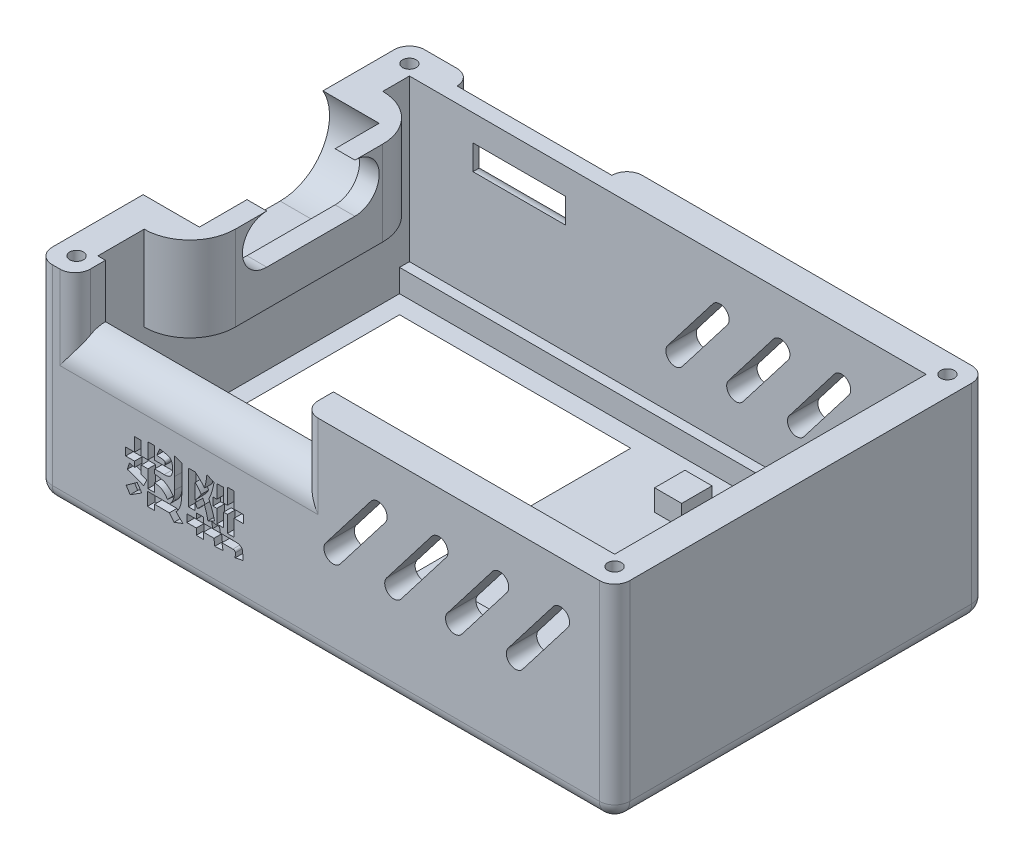
SolidWorks part; units mm, degrees
material "尼龙 6/10"
ref_plane "前视基准面" through (0, 0, 0) normal (0, 0, 1) x (1, 0, 0)
ref_plane "上视基准面" through (0, 0, 0) normal (0, 1, 0) x (1, 0, 0)
ref_plane "右视基准面" through (0, 0, 0) normal (1, 0, 0) x (0, 0, -1)
sketch "草图1" plane through (0, 0, 0) normal (0, 1, 0) x (1, 0, 0)
  line L1 (-72.1576, -30.7504) -> (-34.1576, -30.7504)
  line L2 (-72.1576, -30.7504) -> (-72.1576, -6.2504)
  line L3 (-72.1576, -6.2504) -> (-34.1576, -6.2504)
  line L4 (-34.1576, -30.7504) -> (-34.1576, -6.2504)
  dimension "D1" = 24.5
  dimension "D2" = 38
extrude "凸台-拉伸1" add sketch "草图1" along normal blind 13.58 contours L2 L1 L4 L3
sketch "草图2" plane through (0, 13.58, 0) normal (0, 1, 0) x (1, 0, 0)
  line L0 (-34.1576, -30.7504) -> (-34.1576, -6.2504) construction
  line L1 (-70.1576, -8.2504) -> (-36.1576, -8.2504)
  line L2 (-70.1576, -8.2504) -> (-70.1576, -28.7504)
  line L3 (-70.1576, -28.7504) -> (-36.1576, -28.7504)
  line L4 (-36.1576, -8.2504) -> (-36.1576, -28.7504)
  line L5 (-72.1576, -30.7504) -> (-34.1576, -30.7504) construction
  line L6 (-72.1576, -30.7504) -> (-72.1576, -6.2504) construction
  line L7 (-72.1576, -6.2504) -> (-34.1576, -6.2504) construction
  dimension "D1" = 2
  dimension "D2" = 2
  dimension "D3" = 2
  dimension "D4" = 2
extrude "切除-拉伸1" cut sketch "草图2" against normal blind 10.58
sketch "草图4" plane through (0, 0, 0) normal (0, -1, 0) x (-1, 0, 0)
  line L0 (72.1576, -30.7504) -> (72.1576, -6.2504) construction
  line L1 (68.9576, -10.1004) -> (53.7476, -10.1004)
  line L2 (68.9576, -10.1004) -> (68.9576, -25.3104)
  line L3 (68.9576, -25.3104) -> (53.7476, -25.3104)
  line L4 (53.7476, -10.1004) -> (53.7476, -25.3104)
  line L6 (72.1576, -30.7504) -> (34.1576, -30.7504) construction
  dimension "D1" = 15.21
  dimension "D2" = 15.21
  dimension "D3" = 3.2
  dimension "D4" = 5.44
extrude "切除-拉伸2" cut sketch "草图4" against normal blind 15 contours L2 L1 L4 L3
sketch "草图6" plane through (0, 0, 30.7504) normal (0, 0, 1) x (1, 0, 0)
  line L1 (-54.6576, 10.08) -> (-69.6576, 10.08)
  line L2 (-54.6576, 10.08) -> (-54.6576, 13.58)
  line L3 (-54.6576, 13.58) -> (-69.6576, 13.58)
  line L4 (-69.6576, 10.08) -> (-69.6576, 13.58)
  line L5 (-72.1576, 13.58) -> (-72.1576, 0) construction
  line L6 (-72.1576, 13.58) -> (-34.1576, 13.58) construction
  point P9 (-69.6576, 11.83)
  dimension "D2" = 3.5
  dimension "D3" = 2.5
  dimension "D4" = 15
extrude "切除-拉伸4" cut sketch "草图6" against normal blind 5
sketch "草图11" plane through (0, 3, 0) normal (0, 1, 0) x (1, 0, 0)
  line L0 (-68.9576, -25.3104) -> (-68.9576, -10.1004) construction
  line L1 (-37.6576, -8.9004) -> (-70.1576, -8.9004)
  line L2 (-37.6576, -8.9004) -> (-37.6576, -26.5004)
  line L3 (-37.6576, -26.5004) -> (-70.1576, -26.5004)
  line L4 (-70.1576, -8.9004) -> (-70.1576, -26.5004)
  line L5 (-53.7476, -10.1004) -> (-68.9576, -10.1004) construction
  line L7 (-36.1576, -28.7504) -> (-36.1576, -8.2504) construction
  dimension "D1" = 1.5
  dimension "D2" = 17.6
  dimension "D3" = 1.2
  dimension "D4" = 1.2
extrude "切除-拉伸10" cut sketch "草图11" against normal blind 1.5
fillet "圆角2" radius 1 8 edges at (-34.1576, 6.79, 6.2504) (-53.1576, 0, 6.2504) (-53.1576, 0, 30.7504) (-72.1576, 0, 18.5004) (-72.1576, 6.79, 30.7504) (-34.1576, 6.79, 30.7504) (-34.1576, 0, 18.5004) (-72.1576, 6.79, 6.2504)
chamfer "倒角2" distance 1.5 distance2 1.5 4 edges at (-61.3526, 0, 25.3104) (-53.7476, 0, 17.7054) (-61.3526, 0, 10.1004) (-68.9576, 0, 17.7054)
fillet "圆角8" radius 1 1 edges at (-37.6576, 3, 17.7004) type face fillet first side face at (-37.6576, 2.25, 17.7004) second side face at (-53.5326, 3, 18.1004)
sketch "草图24" plane through (-36.1576, 0, 0) normal (-1, 0, 0) x (0, 0, 1)
  line L1 (21.2004, 3) -> (14.2004, 3)
  line L2 (21.2004, 3) -> (21.2004, 12.5)
  line L3 (21.2004, 12.5) -> (14.2004, 12.5)
  line L4 (14.2004, 3) -> (14.2004, 12.5)
  line L10 (8.9004, 3) -> (26.5004, 3) construction
  point P4 (17.7004, 3)
  dimension "D1" = 9.5
  dimension "D2" = 7
extrude "切除-拉伸17" cut sketch "草图24" against normal blind 1
sketch "草图29" plane through (0, 13.58, 0) normal (0, 1, 0) x (1, 0, 0)
  line L0 (-72.1576, -29.7504) -> (-72.1576, -7.2504) construction
  line L4 (-34.1576, -29.7504) -> (-34.1576, -7.2504) construction
  line L5 (-71.1576, -30.7504) -> (-69.6576, -30.7504) construction
  line L8 (-71.1576, -6.2504) -> (-35.1576, -6.2504) construction
  circle A0 centre (-70.8576, -7.5504) radius 0.45
  circle A1 centre (-70.8576, -29.4504) radius 0.45
  circle A2 centre (-35.4576, -7.5504) radius 0.45
  circle A3 centre (-35.4576, -29.4504) radius 0.45
  dimension "D1" = 0.9
  dimension "D2" = 1.3
  dimension "D3" = 1.3
  dimension "D4" = 1.3
  dimension "D5" = 1.3
extrude "切除-拉伸18" cut sketch "草图29" against normal blind 6
sketch "草图37" plane through (0, 13.58, 0) normal (0, 1, 0) x (1, 0, 0)
  line L0 (-70.1576, -8.2504) -> (-70.1576, -28.7504) construction
  line L1 (-70.1576, -10.0054) -> (-67.1576, -10.0054)
  line L2 (-70.1576, -10.0054) -> (-70.1576, -25.7054)
  line L3 (-70.1576, -25.7054) -> (-67.1576, -25.7054)
  line L4 (-67.1576, -10.0054) -> (-67.1576, -25.7054)
  dimension "D1" = 3
  dimension "D2" = 15.7
extrude "凸台-拉伸8" add sketch "草图37" against normal blind 10
sketch "草图34" plane through (-72.1576, 0, 0) normal (-1, 0, 0) x (0, 0, 1)
  line L0 (20.9554, 11.955) -> (14.7554, 11.955) construction
  line L3 (20.9554, 8.705) -> (14.7554, 8.705)
  line L4 (20.9554, 15.205) -> (14.7554, 15.205)
  line L5 (10.0054, 3.58) -> (10.0054, 13.58) construction
  line L6 (29.7504, 13.58) -> (7.2504, 13.58) construction
  line L12 (7.2504, 1) -> (29.7504, 1) construction
  arc A2 (20.9554, 8.705) -> (20.9554, 15.205) centre (20.9554, 11.955) ccw
  arc A3 (14.7554, 15.205) -> (14.7554, 8.705) centre (14.7554, 11.955) ccw
  point P3 (17.8554, 11.955)
  point P8 (17.8554, 15.205)
  point P15 (18.5004, 1)
  dimension "D3" = 1.625
  dimension "D4" = 4.75
  dimension "D1" = 6.2
  dimension "D2" = 6.5
extrude "切除-拉伸21" cut sketch "草图34" against normal blind 3.7
sketch "草图39" plane through (-68.4576, 0, 0) normal (-1, 0, 0) x (0, 0, 1)
  line L0 (20.6371, 11.98) -> (14.8371, 11.98) construction
  line L1 (20.6371, 10.38) -> (14.8371, 10.38)
  line L2 (20.6371, 13.58) -> (14.8371, 13.58)
  line L3 (11.9408, 13.58) -> (23.77, 13.58) construction
  arc A0 (20.6371, 10.38) -> (20.6371, 13.58) centre (20.6371, 11.98) ccw
  arc A1 (14.8371, 13.58) -> (14.8371, 10.38) centre (14.8371, 11.98) ccw
  point P2 (17.7371, 11.98)
  point P7 (22.2371, 11.98)
  point P8 (13.2371, 11.98)
  dimension "D1" = 3.2
  dimension "D2" = 9
extrude "切除-拉伸24" cut sketch "草图39" against normal blind 9 contours L1 A1 L2 A0
fillet "圆角9" radius 3 2 edges at (-67.1576, 8.58, 10.0054) (-67.1576, 8.58, 25.7054)
sketch "草图42" plane through (0, 0, 6.2504) normal (0, 0, -1) x (-1, 0, 0)
  line L0 (72.1576, 13.58) -> (72.1576, 1) construction
  text T0 "<b><r270>关开</r></b>" font "微软雅黑" height 3
  point P1 (60.1576, 5.864)
  point P2 (60.1576, 6.3989)
  dimension "D1" = 12
extrude "切除-拉伸26" cut sketch "草图42" against normal blind 0.5
sketch "草图43" plane through (0, 0, 30.7504) normal (0, 0, 1) x (1, 0, 0)
  text T0 "<b><r90>选择</r></b>" font "微软雅黑" height 3
  point P0 (-63.0353, 2.8105)
extrude "切除-拉伸27" cut sketch "草图43" against normal blind 0.5
sketch "草图46" plane through (-67.1576, 0, 0) normal (1, 0, 0) x (0, 0, -1)
  line L7 (-8.2504, 3) -> (-8.2504, 13.58) construction
  line L8 (-28.7504, 3) -> (-28.7504, 13.58) construction
  line L19 (-28.7504, 8) -> (-8.2504, 8)
  line L20 (-28.7504, 8) -> (-28.7504, 3)
  line L21 (-28.7504, 3) -> (-8.2504, 3)
  line L22 (-8.2504, 8) -> (-8.2504, 3)
  line L25 (-8.2504, 3) -> (-8.9004, 3) construction
  dimension "D1" = 5
extrude "切除-拉伸29" cut sketch "草图46" against normal up to surface (3 mm away) and the other way up to surface (31 mm away) up to face at (-70.1576, 6.3733, 18.0188) other way up to face at (-36.1576, 8.02, 18.1004)
sketch "草图48" plane through (0, 1.5, 0) normal (0, 1, 0) x (1, 0, 0)
  line L0 (-70.1576, -8.2504) -> (-70.1576, -8.9004) construction
  line L1 (-49.3076, -10.9679) -> (-47.5264, -10.9679)
  line L2 (-49.3076, -10.9679) -> (-49.3076, -12.9679)
  line L3 (-49.3076, -12.9679) -> (-47.5264, -12.9679)
  line L4 (-47.5264, -10.9679) -> (-47.5264, -12.9679)
  line L5 (-49.3076, -25.3179) -> (-47.5264, -25.3179)
  line L6 (-49.3076, -25.3179) -> (-49.3076, -27.3179)
  line L7 (-49.3076, -27.3179) -> (-47.5264, -27.3179)
  line L8 (-47.5264, -25.3179) -> (-47.5264, -27.3179)
  dimension "D1" = 20.85
  dimension "D2" = 2
  dimension "D3" = 12.35
extrude "凸台-拉伸9" add sketch "草图48" along normal blind 1.4
sketch "草图49" plane through (0, 3, 0) normal (0, 1, 0) x (1, 0, 0)
  line L1 (-36.6576, -14.2004) -> (-37.6576, -14.2004)
  line L2 (-36.6576, -14.2004) -> (-36.6576, -21.2004)
  line L3 (-36.6576, -21.2004) -> (-37.6576, -21.2004)
  line L4 (-37.6576, -14.2004) -> (-37.6576, -21.2004)
  line L5 (-37.6576, -26.5004) -> (-37.6576, -8.9004) construction
  line L11 (-36.6576, -8.9004) -> (-36.6576, -26.5004) construction
  point P4 (-36.6576, -17.7004)
  dimension "D1" = 7
extrude "切除-拉伸30" cut sketch "草图49" against normal up to surface (1.5 mm away) up to face at (-48.417, 1.5, 11.9679)
sketch "草图50" plane through (0, 0, 6.2504) normal (0, 0, -1) x (-1, 0, 0)
  line L0 (49.7213, 10.2108) -> (52.6822, 6.3661) construction
  line L1 (50.1967, 10.5769) -> (53.1576, 6.7322)
  line L2 (49.2459, 9.8448) -> (52.2068, 6)
  line L3 (45.7213, 10.2108) -> (48.6822, 6.3661) construction
  line L4 (46.1967, 10.5769) -> (49.1576, 6.7322)
  line L5 (45.2459, 9.8448) -> (48.2068, 6)
  line L6 (41.7213, 10.2108) -> (44.6822, 6.3661) construction
  line L7 (42.1967, 10.5769) -> (45.1576, 6.7322)
  line L8 (41.2459, 9.8448) -> (44.2068, 6)
  line L9 (37.7213, 10.2108) -> (40.6822, 6.3661) construction
  line L10 (38.1967, 10.5769) -> (41.1576, 6.7322)
  line L11 (37.2459, 9.8448) -> (40.2068, 6)
  line L12 (71.1576, 1) -> (71.1576, 13.58) construction
  line L13 (35.1576, 1) -> (71.1576, 1) construction
  arc A0 (50.1967, 10.5769) -> (49.2459, 9.8448) centre (49.7213, 10.2108) ccw
  arc A1 (52.2068, 6) -> (53.1576, 6.7322) centre (52.6822, 6.3661) ccw
  arc A2 (46.1967, 10.5769) -> (45.2459, 9.8448) centre (45.7213, 10.2108) ccw
  arc A3 (48.2068, 6) -> (49.1576, 6.7322) centre (48.6822, 6.3661) ccw
  arc A4 (42.1967, 10.5769) -> (41.2459, 9.8448) centre (41.7213, 10.2108) ccw
  arc A5 (44.2068, 6) -> (45.1576, 6.7322) centre (44.6822, 6.3661) ccw
  arc A6 (38.1967, 10.5769) -> (37.2459, 9.8448) centre (37.7213, 10.2108) ccw
  arc A7 (40.2068, 6) -> (41.1576, 6.7322) centre (40.6822, 6.3661) ccw
  point P2 (51.2018, 8.2885)
  point P11 (47.2018, 8.2885)
  point P18 (43.2018, 8.2885)
  point P25 (39.2018, 8.2885)
  dimension "D4" = 4.8527
  dimension "D2" = 18
  dimension "D3" = 5
  dimension "D1" = 4
extrude "切除-拉伸31" cut sketch "草图50" against normal through all
sketch "草图51" plane through (0, 0, 0) normal (0, -1, 0) x (1, 0, 0)
  line L0 (-50.2476, 26.8104) -> (-48.2476, 26.8104)
  line L1 (-39.1576, 26.8104) -> (-37.1576, 26.8104)
  line L2 (-39.1576, 26.8104) -> (-39.1576, 9.2504)
  line L3 (-39.1576, 9.2504) -> (-37.1576, 9.2504)
  line L4 (-37.1576, 26.8104) -> (-37.1576, 9.2504)
  line L5 (-50.2476, 26.8104) -> (-50.2476, 9.2504)
  line L6 (-50.2476, 9.2504) -> (-48.2476, 9.2504)
  line L7 (-48.2476, 26.8104) -> (-48.2476, 9.2504)
  line L8 (-52.2476, 26.8104) -> (-52.2476, 8.6004) construction
  line L9 (-35.1576, 7.2504) -> (-35.1576, 29.7504) construction
  line L10 (-71.1576, 7.2504) -> (-35.1576, 7.2504) construction
  line L11 (-70.4576, 26.8104) -> (-52.2476, 26.8104) construction
  dimension "D1" = 2
  dimension "D2" = 2
  dimension "D4" = 2
  dimension "D5" = 2
extrude "切除-拉伸32" cut sketch "草图51" against normal blind 0.5
sketch "草图52" plane through (0, 0.5, 0) normal (0, -1, 0) x (1, 0, 0)
  line L0 (-50.2476, 26.8104) -> (-50.2476, 9.2504) construction
  line L1 (-50.2476, 26.5104) -> (-48.2476, 26.5104)
  line L2 (-50.2476, 26.5104) -> (-50.2476, 26.0104)
  line L3 (-50.2476, 26.0104) -> (-48.2476, 26.0104)
  line L4 (-48.2476, 26.5104) -> (-48.2476, 26.0104)
  line L5 (-48.2476, 9.2504) -> (-48.2476, 26.8104) construction
  line L6 (-48.2476, 26.8104) -> (-50.2476, 26.8104) construction
  line L7 (-39.1576, 26.5104) -> (-39.1576, 26.0104)
  line L8 (-39.1576, 26.5104) -> (-37.1576, 26.5104)
  line L9 (-37.1576, 26.5104) -> (-37.1576, 26.0104)
  line L10 (-39.1576, 26.0104) -> (-37.1576, 26.0104)
  line L11 (-39.1576, 25.7486) -> (-39.1576, 25.2486)
  line L12 (-39.1576, 25.7486) -> (-37.1576, 25.7486)
  line L13 (-37.1576, 25.7486) -> (-37.1576, 25.2486)
  line L14 (-39.1576, 25.2486) -> (-37.1576, 25.2486)
  line L15 (-39.1576, 24.9868) -> (-39.1576, 24.4868)
  line L16 (-39.1576, 24.9868) -> (-37.1576, 24.9868)
  line L17 (-37.1576, 24.9868) -> (-37.1576, 24.4868)
  line L18 (-39.1576, 24.4868) -> (-37.1576, 24.4868)
  line L19 (-39.1576, 24.225) -> (-39.1576, 23.725)
  line L20 (-39.1576, 24.225) -> (-37.1576, 24.225)
  line L21 (-37.1576, 24.225) -> (-37.1576, 23.725)
  line L22 (-39.1576, 23.725) -> (-37.1576, 23.725)
  line L23 (-39.1576, 23.4631) -> (-39.1576, 22.9631)
  line L24 (-39.1576, 23.4631) -> (-37.1576, 23.4631)
  line L25 (-37.1576, 23.4631) -> (-37.1576, 22.9631)
  line L26 (-39.1576, 22.9631) -> (-37.1576, 22.9631)
  line L27 (-39.1576, 22.7013) -> (-39.1576, 22.2013)
  line L28 (-39.1576, 22.7013) -> (-37.1576, 22.7013)
  line L29 (-37.1576, 22.7013) -> (-37.1576, 22.2013)
  line L30 (-39.1576, 22.2013) -> (-37.1576, 22.2013)
  line L31 (-39.1576, 21.9395) -> (-39.1576, 21.4395)
  line L32 (-39.1576, 21.9395) -> (-37.1576, 21.9395)
  line L33 (-37.1576, 21.9395) -> (-37.1576, 21.4395)
  line L34 (-39.1576, 21.4395) -> (-37.1576, 21.4395)
  line L35 (-39.1576, 21.1777) -> (-39.1576, 20.6777)
  line L36 (-39.1576, 21.1777) -> (-37.1576, 21.1777)
  line L37 (-37.1576, 21.1777) -> (-37.1576, 20.6777)
  line L38 (-39.1576, 20.6777) -> (-37.1576, 20.6777)
  line L39 (-39.1576, 20.4159) -> (-39.1576, 19.9159)
  line L40 (-39.1576, 20.4159) -> (-37.1576, 20.4159)
  line L41 (-37.1576, 20.4159) -> (-37.1576, 19.9159)
  line L42 (-39.1576, 19.9159) -> (-37.1576, 19.9159)
  line L43 (-39.1576, 19.6541) -> (-39.1576, 19.1541)
  line L44 (-39.1576, 19.6541) -> (-37.1576, 19.6541)
  line L45 (-37.1576, 19.6541) -> (-37.1576, 19.1541)
  line L46 (-39.1576, 19.1541) -> (-37.1576, 19.1541)
  line L47 (-39.1576, 18.8922) -> (-39.1576, 18.3922)
  line L48 (-39.1576, 18.8922) -> (-37.1576, 18.8922)
  line L49 (-37.1576, 18.8922) -> (-37.1576, 18.3922)
  line L50 (-39.1576, 18.3922) -> (-37.1576, 18.3922)
  line L51 (-39.1576, 18.1304) -> (-39.1576, 17.6304)
  line L52 (-39.1576, 18.1304) -> (-37.1576, 18.1304)
  line L53 (-37.1576, 18.1304) -> (-37.1576, 17.6304)
  line L54 (-39.1576, 17.6304) -> (-37.1576, 17.6304)
  line L55 (-39.1576, 17.3686) -> (-39.1576, 16.8686)
  line L56 (-39.1576, 17.3686) -> (-37.1576, 17.3686)
  line L57 (-37.1576, 17.3686) -> (-37.1576, 16.8686)
  line L58 (-39.1576, 16.8686) -> (-37.1576, 16.8686)
  line L59 (-39.1576, 16.6068) -> (-39.1576, 16.1068)
  line L60 (-39.1576, 16.6068) -> (-37.1576, 16.6068)
  line L61 (-37.1576, 16.6068) -> (-37.1576, 16.1068)
  line L62 (-39.1576, 16.1068) -> (-37.1576, 16.1068)
  line L63 (-39.1576, 15.845) -> (-39.1576, 15.345)
  line L64 (-39.1576, 15.845) -> (-37.1576, 15.845)
  line L65 (-37.1576, 15.845) -> (-37.1576, 15.345)
  line L66 (-39.1576, 15.345) -> (-37.1576, 15.345)
  line L67 (-39.1576, 15.0831) -> (-39.1576, 14.5831)
  line L68 (-39.1576, 15.0831) -> (-37.1576, 15.0831)
  line L69 (-37.1576, 15.0831) -> (-37.1576, 14.5831)
  line L70 (-39.1576, 14.5831) -> (-37.1576, 14.5831)
  line L71 (-39.1576, 14.3213) -> (-39.1576, 13.8213)
  line L72 (-39.1576, 14.3213) -> (-37.1576, 14.3213)
  line L73 (-37.1576, 14.3213) -> (-37.1576, 13.8213)
  line L74 (-39.1576, 13.8213) -> (-37.1576, 13.8213)
  line L75 (-50.2476, 25.7486) -> (-50.2476, 25.2486)
  line L76 (-50.2476, 25.7486) -> (-48.2476, 25.7486)
  line L77 (-48.2476, 25.7486) -> (-48.2476, 25.2486)
  line L78 (-50.2476, 25.2486) -> (-48.2476, 25.2486)
  line L79 (-50.2476, 24.9868) -> (-50.2476, 24.4868)
  line L80 (-50.2476, 24.9868) -> (-48.2476, 24.9868)
  line L81 (-48.2476, 24.9868) -> (-48.2476, 24.4868)
  line L82 (-50.2476, 24.4868) -> (-48.2476, 24.4868)
  line L83 (-50.2476, 24.225) -> (-50.2476, 23.725)
  line L84 (-50.2476, 24.225) -> (-48.2476, 24.225)
  line L85 (-48.2476, 24.225) -> (-48.2476, 23.725)
  line L86 (-50.2476, 23.725) -> (-48.2476, 23.725)
  line L87 (-50.2476, 23.4631) -> (-50.2476, 22.9631)
  line L88 (-50.2476, 23.4631) -> (-48.2476, 23.4631)
  line L89 (-48.2476, 23.4631) -> (-48.2476, 22.9631)
  line L90 (-50.2476, 22.9631) -> (-48.2476, 22.9631)
  line L91 (-50.2476, 22.7013) -> (-50.2476, 22.2013)
  line L92 (-50.2476, 22.7013) -> (-48.2476, 22.7013)
  line L93 (-48.2476, 22.7013) -> (-48.2476, 22.2013)
  line L94 (-50.2476, 22.2013) -> (-48.2476, 22.2013)
  line L95 (-50.2476, 21.9395) -> (-50.2476, 21.4395)
  line L96 (-50.2476, 21.9395) -> (-48.2476, 21.9395)
  line L97 (-48.2476, 21.9395) -> (-48.2476, 21.4395)
  line L98 (-50.2476, 21.4395) -> (-48.2476, 21.4395)
  line L99 (-50.2476, 21.1777) -> (-50.2476, 20.6777)
  line L100 (-50.2476, 21.1777) -> (-48.2476, 21.1777)
  line L101 (-48.2476, 21.1777) -> (-48.2476, 20.6777)
  line L102 (-50.2476, 20.6777) -> (-48.2476, 20.6777)
  line L103 (-50.2476, 20.4159) -> (-50.2476, 19.9159)
  line L104 (-50.2476, 20.4159) -> (-48.2476, 20.4159)
  line L105 (-48.2476, 20.4159) -> (-48.2476, 19.9159)
  line L106 (-50.2476, 19.9159) -> (-48.2476, 19.9159)
  line L107 (-50.2476, 19.6541) -> (-50.2476, 19.1541)
  line L108 (-50.2476, 19.6541) -> (-48.2476, 19.6541)
  line L109 (-48.2476, 19.6541) -> (-48.2476, 19.1541)
  line L110 (-50.2476, 19.1541) -> (-48.2476, 19.1541)
  line L111 (-50.2476, 18.8922) -> (-50.2476, 18.3922)
  line L112 (-50.2476, 18.8922) -> (-48.2476, 18.8922)
  line L113 (-48.2476, 18.8922) -> (-48.2476, 18.3922)
  line L114 (-50.2476, 18.3922) -> (-48.2476, 18.3922)
  line L115 (-50.2476, 18.1304) -> (-50.2476, 17.6304)
  line L116 (-50.2476, 18.1304) -> (-48.2476, 18.1304)
  line L117 (-48.2476, 18.1304) -> (-48.2476, 17.6304)
  line L118 (-50.2476, 17.6304) -> (-48.2476, 17.6304)
  line L119 (-50.2476, 17.3686) -> (-50.2476, 16.8686)
  line L120 (-50.2476, 17.3686) -> (-48.2476, 17.3686)
  line L121 (-48.2476, 17.3686) -> (-48.2476, 16.8686)
  line L122 (-50.2476, 16.8686) -> (-48.2476, 16.8686)
  line L123 (-50.2476, 16.6068) -> (-50.2476, 16.1068)
  line L124 (-50.2476, 16.6068) -> (-48.2476, 16.6068)
  line L125 (-48.2476, 16.6068) -> (-48.2476, 16.1068)
  line L126 (-50.2476, 16.1068) -> (-48.2476, 16.1068)
  line L127 (-50.2476, 15.845) -> (-50.2476, 15.345)
  line L128 (-50.2476, 15.845) -> (-48.2476, 15.845)
  line L129 (-48.2476, 15.845) -> (-48.2476, 15.345)
  line L130 (-50.2476, 15.345) -> (-48.2476, 15.345)
  line L131 (-50.2476, 15.0831) -> (-50.2476, 14.5831)
  line L132 (-50.2476, 15.0831) -> (-48.2476, 15.0831)
  line L133 (-48.2476, 15.0831) -> (-48.2476, 14.5831)
  line L134 (-50.2476, 14.5831) -> (-48.2476, 14.5831)
  line L135 (-50.2476, 14.3213) -> (-50.2476, 13.8213)
  line L136 (-50.2476, 14.3213) -> (-48.2476, 14.3213)
  line L137 (-48.2476, 14.3213) -> (-48.2476, 13.8213)
  line L138 (-50.2476, 13.8213) -> (-48.2476, 13.8213)
  line L139 (-50.2476, 13.5595) -> (-50.2476, 13.0595)
  line L140 (-50.2476, 13.5595) -> (-48.2476, 13.5595)
  line L141 (-48.2476, 13.5595) -> (-48.2476, 13.0595)
  line L142 (-50.2476, 13.0595) -> (-48.2476, 13.0595)
  line L143 (-39.1576, 13.5595) -> (-39.1576, 13.0595)
  line L144 (-39.1576, 13.5595) -> (-37.1576, 13.5595)
  line L145 (-37.1576, 13.5595) -> (-37.1576, 13.0595)
  line L146 (-39.1576, 13.0595) -> (-37.1576, 13.0595)
  line L147 (-50.2476, 12.7977) -> (-50.2476, 12.2977)
  line L148 (-50.2476, 12.7977) -> (-48.2476, 12.7977)
  line L149 (-48.2476, 12.7977) -> (-48.2476, 12.2977)
  line L150 (-50.2476, 12.2977) -> (-48.2476, 12.2977)
  line L151 (-39.1576, 12.7977) -> (-39.1576, 12.2977)
  line L152 (-39.1576, 12.7977) -> (-37.1576, 12.7977)
  line L153 (-37.1576, 12.7977) -> (-37.1576, 12.2977)
  line L154 (-39.1576, 12.2977) -> (-37.1576, 12.2977)
  line L155 (-50.2476, 12.0359) -> (-50.2476, 11.5359)
  line L156 (-50.2476, 12.0359) -> (-48.2476, 12.0359)
  line L157 (-48.2476, 12.0359) -> (-48.2476, 11.5359)
  line L158 (-50.2476, 11.5359) -> (-48.2476, 11.5359)
  line L159 (-39.1576, 12.0359) -> (-39.1576, 11.5359)
  line L160 (-39.1576, 12.0359) -> (-37.1576, 12.0359)
  line L161 (-37.1576, 12.0359) -> (-37.1576, 11.5359)
  line L162 (-39.1576, 11.5359) -> (-37.1576, 11.5359)
  line L163 (-50.2476, 11.2741) -> (-50.2476, 10.7741)
  line L164 (-50.2476, 11.2741) -> (-48.2476, 11.2741)
  line L165 (-48.2476, 11.2741) -> (-48.2476, 10.7741)
  line L166 (-50.2476, 10.7741) -> (-48.2476, 10.7741)
  line L167 (-39.1576, 11.2741) -> (-39.1576, 10.7741)
  line L168 (-39.1576, 11.2741) -> (-37.1576, 11.2741)
  line L169 (-37.1576, 11.2741) -> (-37.1576, 10.7741)
  line L170 (-39.1576, 10.7741) -> (-37.1576, 10.7741)
  line L171 (-50.2476, 10.5122) -> (-50.2476, 10.0122)
  line L172 (-50.2476, 10.5122) -> (-48.2476, 10.5122)
  line L173 (-48.2476, 10.5122) -> (-48.2476, 10.0122)
  line L174 (-50.2476, 10.0122) -> (-48.2476, 10.0122)
  line L175 (-39.1576, 10.5122) -> (-39.1576, 10.0122)
  line L176 (-39.1576, 10.5122) -> (-37.1576, 10.5122)
  line L177 (-37.1576, 10.5122) -> (-37.1576, 10.0122)
  line L178 (-39.1576, 10.0122) -> (-37.1576, 10.0122)
  line L179 (-50.2476, 9.7504) -> (-50.2476, 9.2504)
  line L180 (-50.2476, 9.7504) -> (-48.2476, 9.7504)
  line L181 (-48.2476, 9.7504) -> (-48.2476, 9.2504)
  line L182 (-50.2476, 9.2504) -> (-48.2476, 9.2504)
  line L183 (-39.1576, 9.7504) -> (-39.1576, 9.2504)
  line L184 (-39.1576, 9.7504) -> (-37.1576, 9.7504)
  line L185 (-37.1576, 9.7504) -> (-37.1576, 9.2504)
  line L186 (-39.1576, 9.2504) -> (-37.1576, 9.2504)
  line L187 (-39.1576, 26.8104) -> (-39.1576, 9.2504) construction
  line L188 (-39.1576, 9.2504) -> (-37.1576, 9.2504) construction
  dimension "D1" = 0.5
  dimension "D2" = 0.3
  dimension "D3" = 2
  dimension "D4" = 23
extrude "凸台-拉伸10" add sketch "草图52" along normal blind 0.5
sketch "草图54" plane through (0, 0, 0) normal (0, -1, 0) x (-1, 0, 0)
  line L0 (44.3147, -24.5348) -> (44.3147, -23.5348)
  line L1 (46.3147, -25.5348) -> (44.3147, -25.5348)
  line L2 (46.3147, -25.5348) -> (46.3147, -24.5348)
  line L3 (46.3147, -24.5348) -> (44.3147, -24.5348)
  line L4 (41.3147, -25.5348) -> (41.3147, -24.5348)
  line L5 (44.3147, -26.5348) -> (43.3147, -26.5348)
  line L6 (44.3147, -26.5348) -> (44.3147, -25.5348)
  line L7 (44.3147, -23.5348) -> (43.3147, -23.5348)
  line L8 (43.3147, -26.5348) -> (43.3147, -25.5348)
  line L9 (43.3147, -24.5348) -> (43.3147, -23.5348)
  line L10 (43.3147, -25.5348) -> (41.3147, -25.5348)
  line L11 (43.3147, -24.5348) -> (41.3147, -24.5348)
  circle A0 centre (43.8147, -13.4351) radius 2
  point P14 (43.8147, -23.5348)
  dimension "D1" = 4
  dimension "D2" = 1
  dimension "D3" = 1
  dimension "D4" = 2
  dimension "D5" = 2
  dimension "D6" = 1
  dimension "D7" = 1
extrude "切除-拉伸34" cut sketch "草图54" against normal blind 0.5
sketch "草图56" plane through (0, 0, 6.2504) normal (0, 0, -1) x (-1, 0, 0)
  line L1 (68.0243, 13.58) -> (57.8375, 13.58)
  line L2 (68.0243, 13.58) -> (68.0243, 8.4971)
  line L3 (68.0243, 8.4971) -> (57.8375, 8.4971)
  line L4 (57.8375, 13.58) -> (57.8375, 8.4971)
  line L5 (71.1576, 13.58) -> (35.1576, 13.58) construction
extrude "切除-拉伸35" cut sketch "草图56" against normal blind 1
sketch "草图57" plane through (0, 0, 7.2504) normal (0, 0, -1) x (-1, 0, 0)
  line L1 (65.9764, 10.2186) -> (59.8853, 10.2186)
  line L2 (65.9764, 10.2186) -> (65.9764, 11.8585)
  line L3 (65.9764, 11.8585) -> (59.8853, 11.8585)
  line L4 (59.8853, 10.2186) -> (59.8853, 11.8585)
  line L5 (57.8375, 13.58) -> (57.8375, 8.4971) construction
  line L6 (57.8375, 8.4971) -> (68.0243, 8.4971) construction
  point P6 (62.9309, 8.4971)
  point P7 (62.9309, 10.2186)
  point P10 (57.8375, 11.0385)
  point P11 (59.8853, 11.0385)
extrude "切除-拉伸36" cut sketch "草图57" against normal blind 1
fillet "圆角10" radius 1 2 edges at (-54.6576, 11.83, 30.7504) (-69.6576, 11.83, 30.7504)
fillet "圆角11" radius 2 1 edges at (-62.1576, 10.08, 30.7504)
fillet "圆角12" radius 1 7 edges at (-59.8853, 11.0385, 7.2504) (-65.9764, 11.0385, 7.2504) (-57.8375, 11.0385, 6.2504) (-62.9309, 8.4971, 6.2504) (-68.0243, 11.0385, 6.2504) (-62.9309, 11.8585, 7.2504) (-62.9309, 10.2186, 7.2504)
